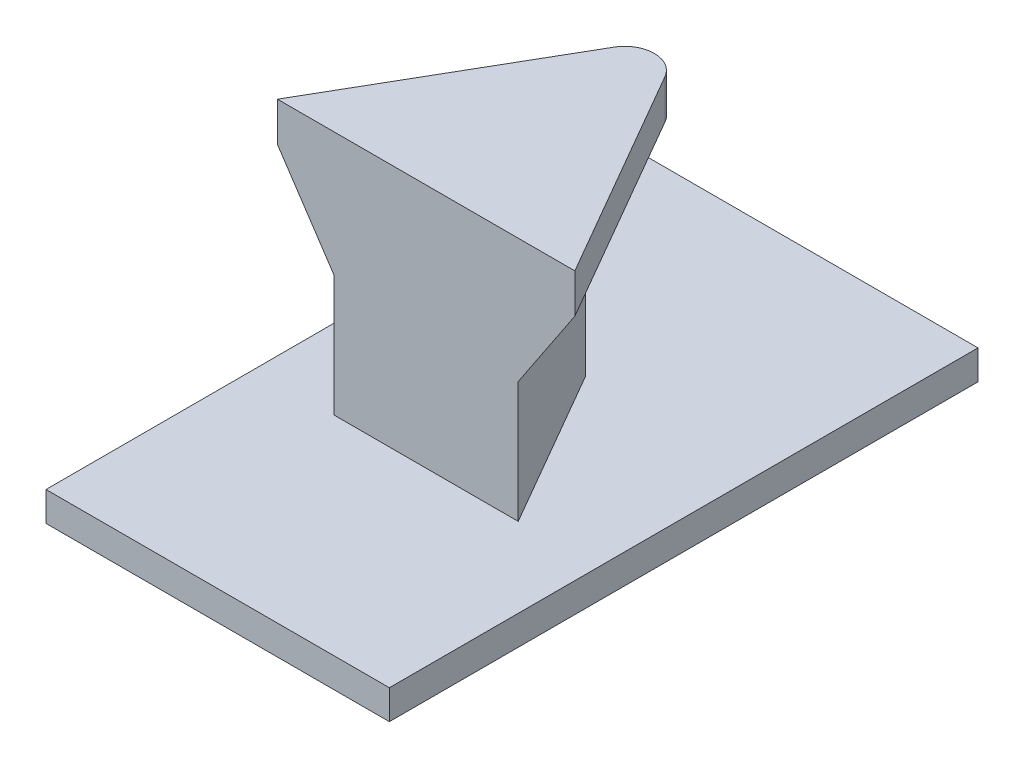
SolidWorks part; units mm, degrees
ref_plane "Front" through (0, 0, 0) normal (0, 0, 1) x (1, 0, 0)
ref_plane "Top" through (0, 0, 0) normal (0, 1, 0) x (1, 0, 0)
ref_plane "Right" through (0, 0, 0) normal (1, 0, 0) x (0, 0, -1)
sketch "Sketch1" plane through (0, 0, 0) normal (0, 1, 0) x (1, 0, 0)
  line L1 (-17.5, -30) -> (17.5, -30)
  line L2 (-17.5, -30) -> (-17.5, 30)
  line L3 (-17.5, 30) -> (17.5, 30)
  line L4 (17.5, -30) -> (17.5, 30)
  line L5 (-17.5, -30) -> (17.5, 30) construction
  line L6 (-17.5, 30) -> (17.5, -30) construction
  point P0 (0, 0)
  dimension "D1" = 35
  dimension "D2" = 60
extrude "Boss-Extrude1" add sketch "Sketch1" along normal blind 3
sketch "Sketch2" plane through (0, 3, 0) normal (0, 1, 0) x (1, 0, 0)
  line L1 (-2.5981, 13) -> (-15.1554, -8.75)
  line L2 (-15.1554, -8.75) -> (15.1554, -8.75)
  line L3 (15.1554, -8.75) -> (2.5981, 13)
  circle A0 centre (0, 0) radius 8.75 construction
  arc A1 (2.5981, 13) -> (-2.5981, 13) centre (0, 11.5) ccw
  dimension "D1" = 3
extrude "Boss-Extrude2" add sketch "Sketch2" along normal blind 25
sketch "Sketch3" plane through (0, 3, 0) normal (0, 1, 0) x (1, 0, 0)
  line L0 (0, 7.5) -> (-9.3819, -8.75)
  line L1 (-6.4952, -3.75) -> (6.4952, -3.75)
  line L2 (9.3819, -8.75) -> (0, 7.5)
  line L3 (-2.5981, 13) -> (-15.1554, -8.75)
  line L4 (-15.1554, -8.75) -> (15.1554, -8.75)
  line L5 (15.1554, -8.75) -> (2.5981, 13)
  line L6 (-2.5981, 13) -> (-15.1554, -8.75)
  line L7 (-15.1554, -8.75) -> (15.1554, -8.75)
  line L8 (15.1554, -8.75) -> (2.5981, 13)
  line L9 (0, 7.5) -> (-6.4952, -3.75) construction
  line L10 (6.4952, -3.75) -> (0, 7.5) construction
  arc A0 (0, 7.5) -> (0, 7.5) centre (0, 7.5) ccw
  arc A1 (2.5981, 13) -> (-2.5981, 13) centre (0, 11.5) ccw
  arc A2 (2.5981, 13) -> (-2.5981, 13) centre (0, 11.5) ccw
  arc M9 (-2.5981, 13) -> (2.5981, 13) centre (0, 11.5) cw
  line M10 (2.5981, 13) -> (15.1554, -8.75)
  line M11 (15.1554, -8.75) -> (-15.1554, -8.75)
  line M12 (-15.1554, -8.75) -> (-2.5981, 13)
  dimension "D1" = 0
  dimension "D2" = 5
extrude "Cut-Extrude1" cut sketch "Sketch3" along normal blind 1 contours L2 L0 M11 M10 M9 M12 region at (-3.5784, 3, -2.066)
chamfer "Chamfer1" distance 20 angle 30 2 edges at (8.8768, 4, -2.125) (-8.8768, 4, -2.125) tangent propagation no first distance on face at (8.8768, 16, -2.125) first distance on face at (-8.8768, 16, -2.125)
